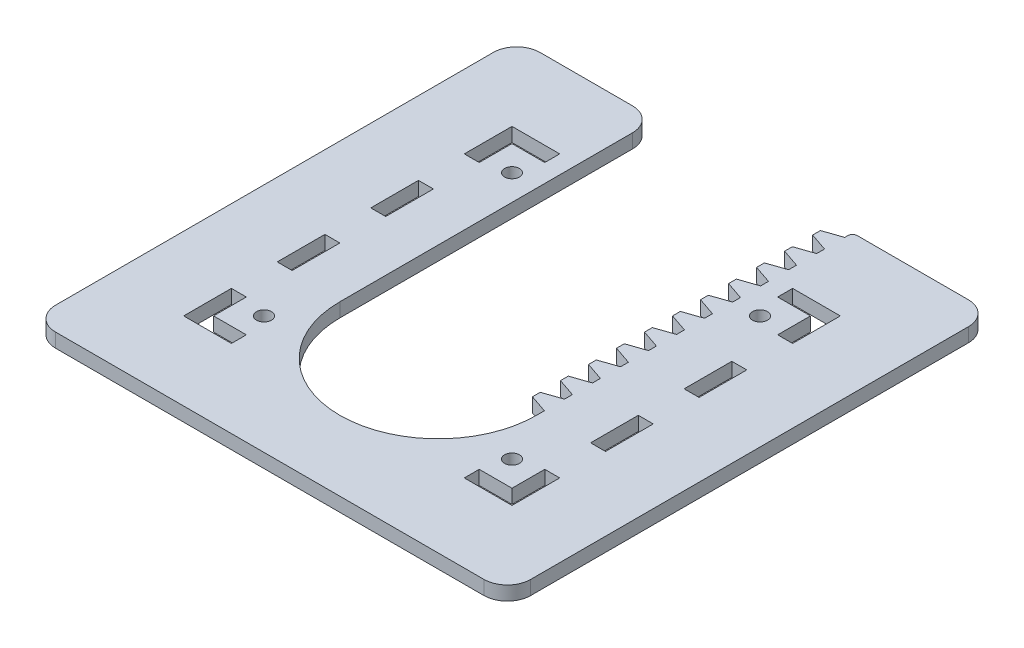
SolidWorks part; units mm, degrees
ref_plane "Front Plane" through (0, 0, 0) normal (0, 0, 1) x (1, 0, 0)
ref_plane "Top Plane" through (0, 0, 0) normal (0, 1, 0) x (1, 0, 0)
ref_plane "Right Plane" through (0, 0, 0) normal (1, 0, 0) x (0, 0, -1)
sketch "Sketch1" plane through (0, 0, 0) normal (0, 1, 0) x (1, 0, 0)
  line L0 (0, 0) -> (0, 21) construction
  line L1 (17.1887, 0) -> (0, 0) construction
  line L2 (21.0585, 3.843) -> (17.1887, 5.1665) construction
  line L3 (17.1887, 5.1665) -> (17.1887, 6.8335) construction
  line L4 (17.1887, 6.8335) -> (21.0585, 8.157) construction
  line L5 (21.0585, 9.843) -> (21.0585, 8.157) construction
  line L6 (21.0585, 9.843) -> (17.1887, 11.1665) construction
  line L7 (17.1887, 11.1665) -> (17.1887, 12.8335) construction
  line L8 (17.1887, 12.8335) -> (21.0585, 14.157) construction
  line L9 (21.0585, 15.843) -> (21.0585, 14.157) construction
  line L10 (21.0585, 15.843) -> (17.1887, 17.1665) construction
  line L11 (17.1887, 17.1665) -> (17.1887, 18.8335) construction
  line L12 (17.1887, 18.8335) -> (21.0585, 20.157) construction
  line L13 (21.0585, 21.843) -> (21.0585, 20.157) construction
  line L14 (21.0585, 21.843) -> (17.1887, 23.1665) construction
  line L15 (17.1887, 23.1665) -> (17.1887, 24.8335) construction
  line L16 (17.1887, 24.8335) -> (21.0585, 26.157) construction
  line L17 (21.0585, 27.843) -> (21.0585, 26.157) construction
  line L18 (21.0585, 27.843) -> (17.1887, 29.1665) construction
  line L19 (17.1887, 29.1665) -> (17.1887, 30.8335) construction
  line L20 (17.1887, 30.8335) -> (21.0585, 32.157) construction
  line L21 (21.0585, 33.843) -> (21.0585, 32.157) construction
  line L22 (21.0585, 33.843) -> (17.1887, 35.1665) construction
  line L23 (17.1887, 35.1665) -> (17.1887, 36.8335) construction
  line L24 (17.1887, 36.8335) -> (21.0585, 38.157) construction
  line L25 (21.0585, 39.843) -> (21.0585, 38.157) construction
  line L26 (21.0585, 39.843) -> (17.1887, 41.1665) construction
  line L27 (17.1887, 41.1665) -> (17.1887, 42.8335) construction
  line L28 (17.1887, 42.8335) -> (21.0585, 44.157) construction
  line L29 (21.0585, 45.843) -> (21.0585, 44.157) construction
  line L30 (21.0585, 45.843) -> (17.1887, 47.1665) construction
  line L31 (17.1887, 47.1665) -> (17.1887, 48.8335) construction
  line L32 (17.1887, 48.8335) -> (21.0585, 50.157) construction
  line L33 (21.0585, 51.843) -> (21.0585, 50.157) construction
  line L34 (21.0585, 51.843) -> (17.1887, 53.1665) construction
  line L35 (17.1887, 53.1665) -> (17.1887, 54.8335) construction
  line L36 (17.1887, 54.8335) -> (21.0585, 56.157) construction
  line L37 (21.0585, 57.843) -> (21.0585, 56.157) construction
  line L38 (21.0585, 57.843) -> (17.1887, 59.1665) construction
  line L39 (17.1887, 59.1665) -> (17.1887, 60.8335) construction
  line L40 (17.1887, 60.8335) -> (21.0585, 62.157) construction
  line L41 (21.0585, 62.157) -> (21.0585, 62.843) construction
  line L42 (45.8722, 63.843) -> (22.0585, 63.843) construction
  line L43 (50.8722, -34.9014) -> (50.8722, 58.843) construction
  line L44 (45.8722, -39.9014) -> (-45.8722, -39.9014) construction
  line L45 (-50.8722, 58.843) -> (-50.8722, -34.9014) construction
  line L46 (-45.8722, 63.843) -> (-22.0585, 63.843) construction
  line L47 (-21.0585, -3.843) -> (-21.0585, 62.843) construction
  line L48 (21.0585, -2.157) -> (21.0585, -3.843) construction
  line L49 (21.0585, -2.157) -> (17.1887, -0.8335) construction
  line L50 (17.1887, -0.8335) -> (17.1887, 0.8335) construction
  line L51 (17.1887, 0.8335) -> (21.0585, 2.157) construction
  line L52 (21.0585, 3.843) -> (21.0585, 2.157) construction
  line L53 (21.0585, 3.843) -> (17.1887, 5.1665)
  line L54 (17.1887, 5.1665) -> (17.1887, 6.8335)
  line L55 (17.1887, 6.8335) -> (21.0585, 8.157)
  line L56 (21.0585, 9.843) -> (21.0585, 8.157)
  line L57 (21.0585, 9.843) -> (17.1887, 11.1665)
  line L58 (17.1887, 11.1665) -> (17.1887, 12.8335)
  line L59 (17.1887, 12.8335) -> (21.0585, 14.157)
  line L60 (21.0585, 15.843) -> (21.0585, 14.157)
  line L61 (21.0585, 15.843) -> (17.1887, 17.1665)
  line L62 (17.1887, 17.1665) -> (17.1887, 18.8335)
  line L63 (17.1887, 18.8335) -> (21.0585, 20.157)
  line L64 (21.0585, 21.843) -> (21.0585, 20.157)
  line L65 (21.0585, 21.843) -> (17.1887, 23.1665)
  line L66 (17.1887, 23.1665) -> (17.1887, 24.8335)
  line L67 (17.1887, 24.8335) -> (21.0585, 26.157)
  line L68 (21.0585, 27.843) -> (21.0585, 26.157)
  line L69 (21.0585, 27.843) -> (17.1887, 29.1665)
  line L70 (17.1887, 29.1665) -> (17.1887, 30.8335)
  line L71 (17.1887, 30.8335) -> (21.0585, 32.157)
  line L72 (21.0585, 33.843) -> (21.0585, 32.157)
  line L73 (21.0585, 33.843) -> (17.1887, 35.1665)
  line L74 (17.1887, 35.1665) -> (17.1887, 36.8335)
  line L75 (17.1887, 36.8335) -> (21.0585, 38.157)
  line L76 (21.0585, 39.843) -> (21.0585, 38.157)
  line L77 (21.0585, 39.843) -> (17.1887, 41.1665)
  line L78 (17.1887, 41.1665) -> (17.1887, 42.8335)
  line L79 (17.1887, 42.8335) -> (21.0585, 44.157)
  line L80 (21.0585, 45.843) -> (21.0585, 44.157)
  line L81 (21.0585, 45.843) -> (17.1887, 47.1665)
  line L82 (17.1887, 47.1665) -> (17.1887, 48.8335)
  line L83 (17.1887, 48.8335) -> (21.0585, 50.157)
  line L84 (21.0585, 51.843) -> (21.0585, 50.157)
  line L85 (21.0585, 51.843) -> (17.1887, 53.1665)
  line L86 (17.1887, 53.1665) -> (17.1887, 54.8335)
  line L87 (17.1887, 54.8335) -> (21.0585, 56.157)
  line L88 (21.0585, 57.843) -> (21.0585, 56.157)
  line L89 (21.0585, 57.843) -> (17.1887, 59.1665)
  line L90 (17.1887, 59.1665) -> (17.1887, 60.8335)
  line L91 (17.1887, 60.8335) -> (21.0585, 62.157)
  line L92 (21.0585, 62.157) -> (21.0585, 62.843)
  line L93 (45.8722, 63.843) -> (22.0585, 63.843)
  line L94 (50.8722, -34.9014) -> (50.8722, 58.843)
  line L95 (45.8722, -39.9014) -> (-45.8722, -39.9014)
  line L96 (-50.8722, 58.843) -> (-50.8722, -34.9014)
  line L97 (-45.8722, 63.843) -> (-26.0585, 63.843)
  line L98 (-21.0585, -3.843) -> (-21.0585, 58.843)
  line L99 (21.0585, -2.157) -> (21.0585, -3.843)
  line L100 (21.0585, -2.157) -> (17.1887, -0.8335)
  line L101 (17.1887, -0.8335) -> (17.1887, 0.8335)
  line L102 (17.1887, 0.8335) -> (21.0585, 2.157)
  line L103 (21.0585, 3.843) -> (21.0585, 2.157)
  line L104 (0, 63.843) -> (0, -39.9014) construction
  line L105 (-51.8722, 11.9708) -> (51.8722, 11.9708) construction
  line L106 (0, 11.9708) -> (-51.8722, -39.9014) construction
  line L107 (51.8722, -24.9014) -> (-51.8722, -24.9014) construction
  line L108 (-36.8722, -39.9014) -> (-36.8722, 63.843) construction
  line L109 (36.8722, -39.9014) -> (36.8722, 63.843) construction
  line L110 (45.8722, -39.9014) -> (51.8722, -39.9014) construction
  line L111 (51.8722, -39.9014) -> (51.8722, 63.843) construction
  line L112 (51.8722, 63.843) -> (-51.8722, 63.843) construction
  line L113 (17.1887, 60) -> (0, 60) construction
  line L114 (-51.8722, 63.843) -> (-51.8722, -39.9014) construction
  line L115 (-51.8722, -39.9014) -> (-45.8722, -39.9014) construction
  circle A0 centre (0, 0) radius 21 construction
  circle A1 centre (0, 60) radius 21 construction
  arc A2 (22.0585, 63.843) -> (21.0585, 62.843) centre (22.0585, 62.843) ccw construction
  arc A3 (50.8722, 58.843) -> (45.8722, 63.843) centre (45.8722, 58.843) ccw construction
  arc A4 (45.8722, -39.9014) -> (50.8722, -34.9014) centre (45.8722, -34.9014) ccw construction
  arc A5 (-50.8722, -34.9014) -> (-45.8722, -39.9014) centre (-45.8722, -34.9014) ccw construction
  arc A6 (-45.8722, 63.843) -> (-50.8722, 58.843) centre (-45.8722, 58.843) ccw construction
  arc A8 (-21.0585, -3.843) -> (21.0585, -3.843) centre (0, -3.843) ccw construction
  arc A9 (22.0585, 63.843) -> (21.0585, 62.843) centre (22.0585, 62.843) ccw
  arc A10 (50.8722, 58.843) -> (45.8722, 63.843) centre (45.8722, 58.843) ccw
  arc A11 (45.8722, -39.9014) -> (50.8722, -34.9014) centre (45.8722, -34.9014) ccw
  arc A12 (-50.8722, -34.9014) -> (-45.8722, -39.9014) centre (-45.8722, -34.9014) ccw
  arc A13 (-45.8722, 63.843) -> (-50.8722, 58.843) centre (-45.8722, 58.843) ccw
  arc A14 (-21.0585, 58.843) -> (-26.0585, 63.843) centre (-26.0585, 58.843) ccw
  arc A15 (-21.0585, -3.843) -> (21.0585, -3.843) centre (0, -3.843) ccw
  circle A16 centre (26.5585, -14.5877) radius 1.6 construction
  circle A17 centre (-26.5585, -14.5877) radius 1.6 construction
  circle A18 centre (-26.5585, 38.5292) radius 1.6 construction
  circle A19 centre (26.5585, 38.5292) radius 1.6 construction
  circle A20 centre (26.5585, -14.5877) radius 1.6
  circle A21 centre (-26.5585, -14.5877) radius 1.6
  circle A22 centre (-26.5585, 38.5292) radius 1.6
  circle A23 centre (26.5585, 38.5292) radius 1.6
  circle A24 centre (0, 60) radius 21 construction
sketch "Sketch2" plane through (0, 0, 0) normal (0, 0, 1) x (1, 0, 0)
  line L0 (0, 0) -> (0, 3) construction
  line L1 (-50.8722, 0) -> (50.8722, 0)
  line L2 (-50.8722, 0) -> (-50.8722, 3)
  line L3 (-50.8722, 3) -> (50.8722, 3)
  line L4 (50.8722, 0) -> (50.8722, 3)
  line L5 (-50.8722, 3) -> (-51.8722, 3) construction
  line L6 (-51.8722, 3) -> (-51.8722, 3.75) construction
  line L7 (-51.8722, 3.75) -> (51.8722, 3.75) construction
  line L8 (51.8722, 3.75) -> (51.8722, 3) construction
  line L9 (51.8722, 3) -> (50.8722, 3) construction
  line L10 (50.8722, 0) -> (51.8722, 0) construction
  line L11 (51.8722, 0) -> (51.8722, -0.75) construction
  line L12 (51.8722, -0.75) -> (-51.8722, -0.75) construction
  line L13 (-51.8722, -0.75) -> (-51.8722, 0) construction
  line L14 (-51.8722, 0) -> (-50.8722, 0) construction
  line L15 (59.7, 48.5) -> (59.7, 45.5) construction
  dimension "D2" = 0.75
extrude "Boss-Extrude1" add sketch "Sketch1" along normal up to vertex (3 mm away) up to point (-50.8722, 3, 0)
ref_plane "edge" through (0, 0, -63.843) normal (0, 0, 1) x (1, 0, 0)
sketch "Sketch4" plane through (0, 0, 0) normal (0, 1, 0) x (1, 0, 0)
  line L12 (-25.0418, -23.0877) -> (-25.0418, -20.0877) construction
  line L13 (-15.0251, -23.0877) -> (-15.0251, -20.0877) construction
  line L14 (-5.0084, -23.0877) -> (-5.0084, -20.0877) construction
  line L15 (5.0084, -23.0877) -> (5.0084, -20.0877) construction
  line L16 (15.0251, -23.0877) -> (15.0251, -20.0877) construction
  line L17 (25.0418, -20.0877) -> (25.0418, -23.0877) construction
  line L18 (32.0585, -20.0877) -> (35.0585, -20.0877) construction
  line L30 (-25.0418, -23.0877) -> (-25.0418, -20.0877)
  line L31 (-15.0251, -23.0877) -> (-15.0251, -20.0877)
  line L32 (-5.0084, -23.0877) -> (-5.0084, -20.0877)
  line L33 (5.0084, -23.0877) -> (5.0084, -20.0877)
  line L34 (15.0251, -23.0877) -> (15.0251, -20.0877)
  line L35 (25.0418, -20.0877) -> (25.0418, -23.0877)
  line L36 (-35.0585, 47.0292) -> (35.0585, 47.0292) construction
  line L37 (-32.0585, 44.0292) -> (32.0585, 44.0292) construction
  line L38 (-32.0585, -20.0877) -> (-32.0585, 44.0292) construction
  line L39 (-35.0585, -23.0877) -> (-35.0585, 47.0292) construction
  line L40 (-32.0585, -20.0877) -> (32.0585, -20.0877) construction
  line L41 (-35.0585, -23.0877) -> (35.0585, -23.0877) construction
  line L42 (32.0585, -20.0877) -> (32.0585, 44.0292) construction
  line L43 (35.0585, -23.0877) -> (35.0585, 47.0292) construction
  line L44 (-35.0585, 47.0292) -> (35.0585, 47.0292)
  line L45 (-32.0585, 44.0292) -> (32.0585, 44.0292)
  line L46 (-32.0585, -20.0877) -> (-32.0585, 44.0292)
  line L47 (-35.0585, -23.0877) -> (-35.0585, 47.0292)
  line L48 (-32.0585, -20.0877) -> (32.0585, -20.0877)
  line L49 (-35.0585, -23.0877) -> (35.0585, -23.0877)
  line L50 (32.0585, -20.0877) -> (32.0585, 44.0292)
  line L51 (35.0585, -23.0877) -> (35.0585, 47.0292)
  line L52 (-23.0585, 44.0292) -> (-23.0585, 47.0292) construction
  line L53 (-23.0585, 44.0292) -> (-23.0585, 47.0292)
  line L54 (23.0585, 44.0292) -> (23.0585, 47.0292) construction
  line L55 (23.0585, 44.0292) -> (23.0585, 47.0292)
  line L56 (-32.0585, 44.0292) -> (-35.0585, 44.0292) construction
  line L57 (-25.0418, 47.0292) -> (-25.0418, 44.0292) construction
  line L58 (25.0418, 47.0292) -> (25.0418, 44.0292) construction
  line L59 (32.0585, 47.0292) -> (32.0585, 44.0292) construction
  line L66 (-32.0585, -20.0877) -> (-32.0585, -23.0877) construction
sketch "Sketch3" plane through (0, 0, 0) normal (0, 1, 0) x (1, 0, 0)
  line L0 (32.0585, 37.0125) -> (35.0585, 37.0125) construction
  line L1 (25.0418, 47.0292) -> (25.0418, 44.0292) construction
  line L2 (25.0418, 44.0292) -> (32.0585, 44.0292) construction
  line L3 (32.0585, 44.0292) -> (32.0585, 37.0125) construction
  line L4 (32.0585, 37.0125) -> (35.0585, 37.0125) construction
  line L5 (35.0585, 37.0125) -> (35.0585, 47.0292) construction
  line L6 (35.0585, 47.0292) -> (25.0418, 47.0292) construction
  line L7 (35.0585, -23.0877) -> (35.0585, 47.0292) construction
  line L8 (32.0585, 11.9708) -> (0, 11.9708) construction
  line L9 (0, 11.9708) -> (0, 44.0292) construction
  line L10 (32.0585, 11.9708) -> (0, 11.9708) construction
  line L11 (0, 11.9708) -> (0, 44.0292) construction
  line L13 (35.0585, 26.9958) -> (32.0585, 26.9958) construction
  line L14 (35.0585, 16.9791) -> (32.0585, 16.9791) construction
  line L15 (32.0585, -20.0877) -> (32.0585, 44.0292) construction
  line L16 (35.0585, 26.9958) -> (32.0585, 26.9958) construction
  line L17 (35.0585, 26.9958) -> (35.0585, 16.9791) construction
  line L18 (35.0585, 16.9791) -> (32.0585, 16.9791) construction
  line L19 (32.0585, 26.9958) -> (32.0585, 16.9791) construction
  line L20 (35.1585, 27.0958) -> (35.1585, 16.8791)
  line L21 (35.1585, 16.8791) -> (31.9585, 16.8791)
  line L22 (31.9585, 27.0958) -> (31.9585, 16.8791)
  line L23 (35.1585, 27.0958) -> (31.9585, 27.0958)
  line L24 (35.1585, 36.9125) -> (35.1585, 47.1292)
  line L25 (35.1585, 47.1292) -> (24.9418, 47.1292)
  line L26 (24.9418, 47.1292) -> (24.9418, 43.9292)
  line L27 (24.9418, 43.9292) -> (31.9585, 43.9292)
  line L28 (31.9585, 43.9292) -> (31.9585, 36.9125)
  line L29 (31.9585, 36.9125) -> (35.1585, 36.9125)
  line L30 (35.1585, -3.1543) -> (31.9585, -3.1543)
  line L31 (31.9585, -3.1543) -> (31.9585, 7.0624)
  line L32 (35.1585, 7.0624) -> (31.9585, 7.0624)
  line L33 (35.1585, -3.1543) -> (35.1585, 7.0624)
  line L34 (31.9585, -19.9877) -> (31.9585, -12.971)
  line L35 (24.9418, -19.9877) -> (31.9585, -19.9877)
  line L36 (24.9418, -23.1877) -> (24.9418, -19.9877)
  line L37 (35.1585, -23.1877) -> (24.9418, -23.1877)
  line L38 (35.1585, -12.971) -> (35.1585, -23.1877)
  line L39 (31.9585, -12.971) -> (35.1585, -12.971)
  line L40 (-31.9585, 43.9292) -> (-31.9585, 36.9125)
  line L41 (-24.9418, 43.9292) -> (-31.9585, 43.9292)
  line L42 (-24.9418, 47.1292) -> (-24.9418, 43.9292)
  line L43 (-35.1585, 47.1292) -> (-24.9418, 47.1292)
  line L44 (-35.1585, 36.9125) -> (-35.1585, 47.1292)
  line L45 (-31.9585, 36.9125) -> (-35.1585, 36.9125)
  line L46 (-35.1585, 27.0958) -> (-35.1585, 16.8791)
  line L47 (-35.1585, 16.8791) -> (-31.9585, 16.8791)
  line L48 (-31.9585, 27.0958) -> (-31.9585, 16.8791)
  line L49 (-35.1585, 27.0958) -> (-31.9585, 27.0958)
  line L50 (-35.1585, -3.1543) -> (-31.9585, -3.1543)
  line L51 (-31.9585, -3.1543) -> (-31.9585, 7.0624)
  line L52 (-35.1585, 7.0624) -> (-31.9585, 7.0624)
  line L53 (-35.1585, -3.1543) -> (-35.1585, 7.0624)
  line L54 (-35.1585, -12.971) -> (-35.1585, -23.1877)
  line L55 (-31.9585, -12.971) -> (-35.1585, -12.971)
  line L56 (-31.9585, -19.9877) -> (-31.9585, -12.971)
  line L57 (-24.9418, -19.9877) -> (-31.9585, -19.9877)
  line L58 (-24.9418, -23.1877) -> (-24.9418, -19.9877)
  line L59 (-35.1585, -23.1877) -> (-24.9418, -23.1877)
  dimension "D1" = 0.1
extrude "Cut-Extrude1" cut sketch "Sketch3" along normal through all
